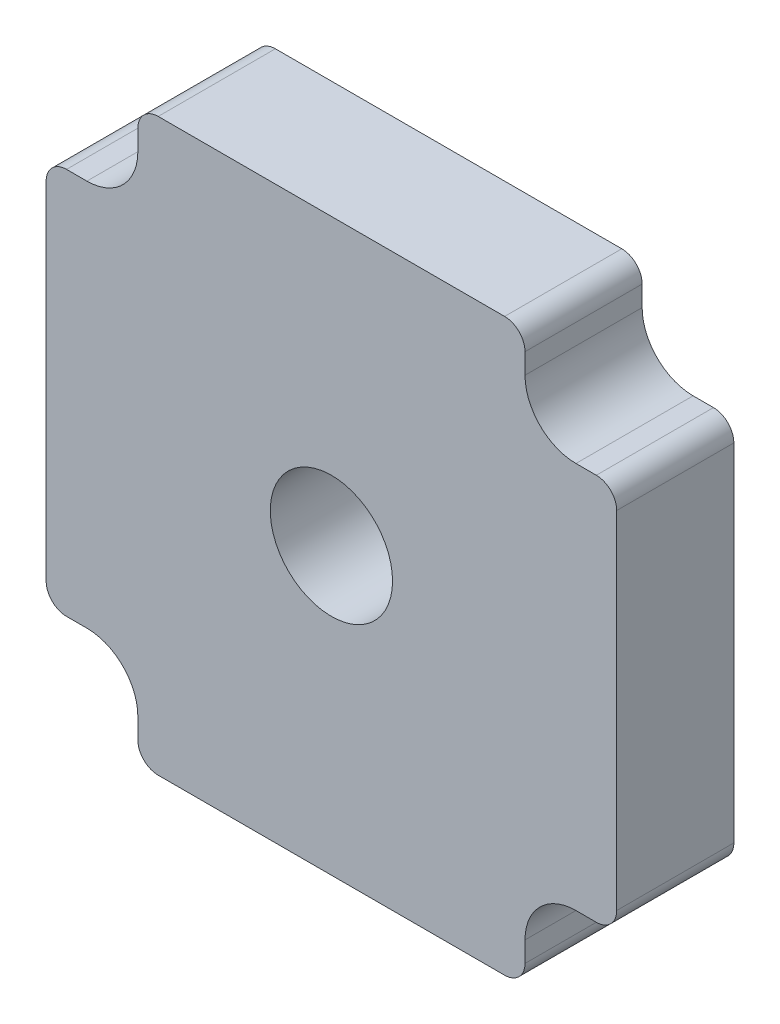
SolidWorks part; units mm, degrees
material "1060 Alloy"
ref_plane "Front Plane" through (0, 0, 0) normal (0, 0, 1) x (1, 0, 0)
ref_plane "Top Plane" through (0, 0, 0) normal (0, 1, 0) x (1, 0, 0)
ref_plane "Right Plane" through (0, 0, 0) normal (1, 0, 0) x (0, 0, -1)
sketch "Sketch1" plane through (0, 0, 0) normal (0, 0, 1) x (1, 0, 0)
  line L1 (28, -28) -> (-28, -28)
  line L2 (28, -28) -> (28, 28)
  line L3 (28, 28) -> (-28, 28)
  line L4 (-28, -28) -> (-28, 28)
  line L5 (28, -28) -> (-28, 28) construction
  line L6 (28, 28) -> (-28, -28) construction
  point P0 (0, 0)
  dimension "D1" = 56
  dimension "D2" = 56
extrude "Boss-Extrude1" add sketch "Sketch1" along normal blind 11.5
ref_axis "Axis1" through (0, 0, -0.575) along (0, 0, 1)
sketch "Sketch2" plane through (0, 0, 11.5) normal (0, 0, 1) x (1, 0, 0)
  line L0 (19, 28) -> (19, 19)
  line L1 (28, 28) -> (-28, 28) construction
  line L2 (19, 19) -> (28, 19)
  line L3 (28, -28) -> (28, 28) construction
  line L4 (28, 19) -> (28, 28)
  line L5 (28, 28) -> (19, 28)
  dimension "D1" = 9
  dimension "D2" = 9
extrude "Cut-Extrude1" cut sketch "Sketch2" against normal blind 11.5
pattern_circular "CirPattern1" count 4 over 360 about axis through (0, 0, -0.575) along (0, 0, 1) of "Cut-Extrude1"
fillet "Fillet1" radius 5 4 edges at (-19, 19, 5.75) (-19, -19, 5.75) (19, -19, 5.75) (19, 19, 5.75)
fillet "Fillet2" radius 2 8 edges at (-28, 19, 5.75) (-19, 28, 5.75) (-19, -28, 5.75) (-28, -19, 5.75) (19, -28, 5.75) (28, -19, 5.75) (28, 19, 5.75) (19, 28, 5.75)
sketch "Sketch3" plane through (0, 0, 11.5) normal (0, 0, 1) x (1, 0, 0)
  circle A0 centre (0, 0) radius 6
  dimension "D1" = 12
extrude "Cut-Extrude2" cut sketch "Sketch3" against normal blind 11.5
